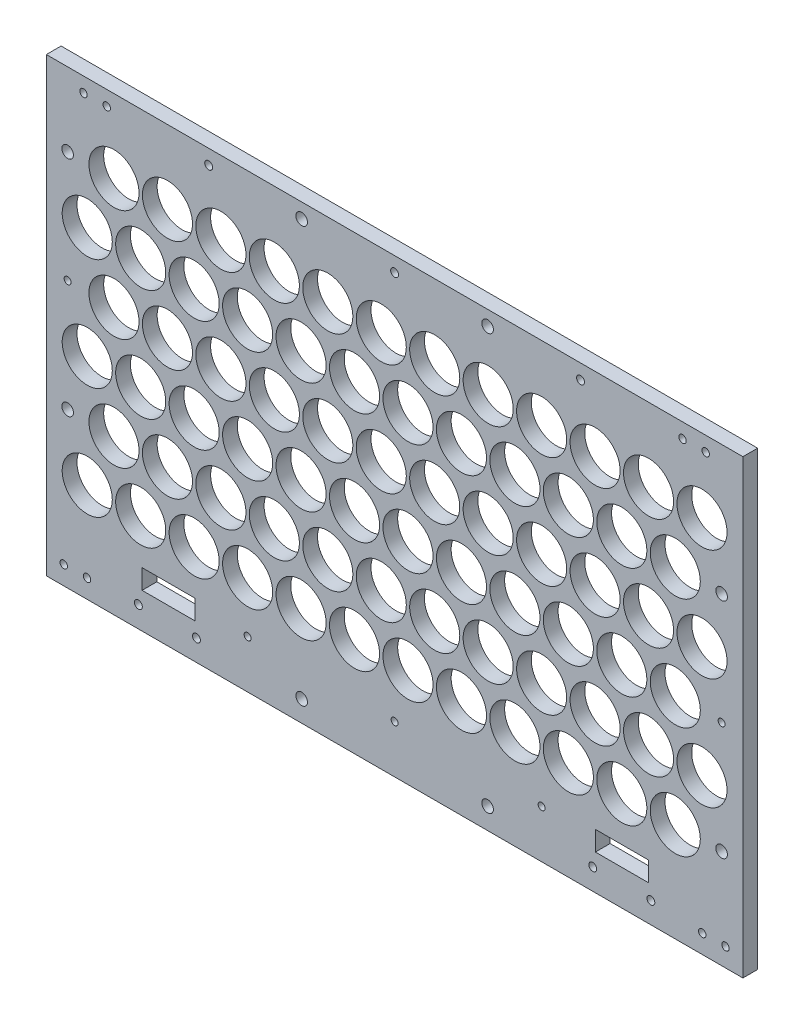
SolidWorks part; units mm, degrees
material "ABS"
ref_plane "X-Y Datum" through (0, 0, 0) normal (0, 0, 1) x (1, 0, 0)
ref_plane "X-Z Datum" through (0, 0, 0) normal (0, 1, 0) x (1, 0, 0)
ref_plane "Y-Z Datum" through (0, 0, 0) normal (1, 0, 0) x (0, 0, -1)
sketch "Sketch1" plane through (0, 0, 0) normal (0, 0, 1) x (1, 0, 0)
  line L1 (-143.025, 70.775) -> (143.025, 70.775)
  line L2 (-143.025, 70.775) -> (-143.025, -70.775)
  line L3 (-143.025, -70.775) -> (143.025, -70.775)
  line L4 (143.025, 70.775) -> (143.025, -70.775)
  line L5 (-143.025, 70.775) -> (143.025, -70.775) construction
  line L6 (-143.025, -70.775) -> (143.025, 70.775) construction
  line L13 (-149.85, -102.6) -> (149.85, -102.6)
  line L14 (-149.85, 91.65) -> (149.85, 91.65)
  line L15 (-149.85, 91.65) -> (-149.85, -102.6)
  line L16 (149.85, 91.65) -> (149.85, -102.6)
  line L17 (149.85, 70.775) -> (149.85, -70.775) construction
  line L18 (-143.025, 91.65) -> (143.025, 91.65) construction
  line L19 (-143.025, -102.6) -> (143.025, -102.6) construction
  line L20 (-149.85, 70.775) -> (-149.85, -70.775) construction
  line L21 (-132.25, -60) -> (-109.25, -60) construction
  circle A0 centre (-132.25, -60) radius 10.775
  circle A1 centre (-109.25, -60) radius 10.775 construction
  circle A2 centre (-120.75, -36) radius 10.775
  point P0 (0, 0)
  point P16 (-120.75, -60)
  dimension "D1" = 21.55
  dimension "D2" = 23
  dimension "D3" = 24
  dimension "D5" = 141.55
  dimension "D6" = 286.05
  dimension "D7" = 31.825
  dimension "D8" = 20.875
  dimension "D9" = 6.825
  dimension "D10" = 6.825
extrude "Boss-Extrude1" add sketch "Sketch1" along normal blind 6.35 contours A0 L3 L4 L1 L2 A2 | A2 | A0 | A0 L2 L3 | L1 L4 L3 L2 region at (2.4105, 0.9241, 0) region at (-140.6182, -68.3682, 0) region at (-132.25, -60, 0) region at (-146.2785, -5.475, 0) region at (-120.75, -36, 0)
sketch "Sketch3" plane through (0, 0, 6.35) normal (0, 0, 1) x (1, 0, 0)
  line L4 (143.025, 70.775) -> (-143.025, 70.775)
  line L5 (143.025, -70.775) -> (143.025, 70.775)
  line L6 (-143.025, -70.775) -> (143.025, -70.775)
  line L7 (-143.025, 70.775) -> (-143.025, -70.775)
  line L8 (143.025, 70.775) -> (-143.025, 70.775)
  line L9 (143.025, -70.775) -> (143.025, 70.775)
  line L10 (-143.025, -70.775) -> (143.025, -70.775)
  line L11 (-143.025, 70.775) -> (-143.025, -70.775)
  circle A1 centre (-120.75, -36) radius 10.775
  circle A2 centre (-120.75, -36) radius 10.775
  circle A3 centre (-132.25, -60) radius 10.775
  circle A4 centre (-132.25, -60) radius 10.775
  dimension "D1" = 0
  dimension "D2" = 0
  dimension "D3" = 0
extrude "Cut-Extrude1" cut sketch "Sketch3" against normal through all contours A4 region at (-132.25, -60, 6.35)
sketch "Sketch4" plane through (0, 0, 6.35) normal (0, 0, 1) x (1, 0, 0)
  line L4 (143.025, 70.775) -> (-143.025, 70.775)
  line L5 (143.025, -70.775) -> (143.025, 70.775)
  line L6 (-143.025, -70.775) -> (143.025, -70.775)
  line L7 (-143.025, 70.775) -> (-143.025, -70.775)
  line L8 (143.025, 70.775) -> (-143.025, 70.775)
  line L9 (143.025, -70.775) -> (143.025, 70.775)
  line L10 (-143.025, -70.775) -> (143.025, -70.775)
  line L11 (-143.025, 70.775) -> (-143.025, -70.775)
  circle A1 centre (-120.75, -36) radius 10.775
  circle A2 centre (-120.75, -36) radius 10.775
  circle A3 centre (-132.25, -60) radius 10.775
  circle A4 centre (-132.25, -60) radius 10.775
  dimension "D1" = 0
  dimension "D2" = 0
  dimension "D3" = 0
extrude "Cut-Extrude2" cut sketch "Sketch4" against normal through all contours A2 region at (-120.75, -36, 6.35)
pattern_linear "LPattern1" count 12 spacing 23 along (1, 0, 0) of "Cut-Extrude1", "Cut-Extrude2"
pattern_linear "LPattern2" count 3 spacing 48 along (0, 1, 0) of "LPattern1"
sketch "Sketch5" plane through (0, 0, 6.35) normal (0, 0, 1) x (1, 0, 0)
  line L4 (105.3154, -79.3475) -> (90.1846, -79.3475)
  line L5 (90.37, -80.3) -> (90.37, -83.4115)
  line L6 (90.37, -83.4115) -> (105.13, -83.4115)
  line L7 (105.13, -83.4115) -> (105.13, -80.3)
  line L8 (105.3154, -79.3475) -> (90.1846, -79.3475)
  line L9 (90.37, -80.3) -> (90.37, -83.4115)
  line L10 (90.37, -83.4115) -> (105.13, -83.4115)
  line L11 (105.13, -83.4115) -> (105.13, -80.3)
  line L12 (-108.668, -78.95) -> (-108.668, -87.4115)
  line L13 (-108.668, -87.4115) -> (-85.908, -87.4115)
  line L14 (-85.908, -87.4115) -> (-85.908, -78.95)
  line L15 (86.37, -78.95) -> (86.37, -87.4115)
  line L16 (-89.7226, -79.3475) -> (-104.8534, -79.3475)
  line L17 (-104.668, -80.3) -> (-104.668, -83.4115)
  line L18 (-104.668, -83.4115) -> (-89.908, -83.4115)
  line L19 (-89.908, -83.4115) -> (-89.908, -80.3)
  line L20 (-89.7226, -79.3475) -> (-104.8534, -79.3475)
  line L21 (-104.668, -80.3) -> (-104.668, -83.4115)
  line L22 (-104.668, -83.4115) -> (-89.908, -83.4115)
  line L23 (-89.908, -83.4115) -> (-89.908, -80.3)
  line L24 (86.37, -87.4115) -> (109.13, -87.4115)
  line L25 (109.13, -87.4115) -> (109.13, -78.95)
  line L26 (149.85, -78.95) -> (-149.85, -78.95) construction
  line L27 (149.85, -78.95) -> (-149.85, -78.95)
  line L28 (109.13, -87.4115) -> (109.13, -80.3) construction
  line L29 (86.37, -80.3) -> (86.37, -87.4115) construction
  line L30 (-85.908, -87.4115) -> (-85.908, -80.3) construction
  line L31 (-108.668, -80.3) -> (-108.668, -87.4115) construction
  arc A2 (90.37, -80.3) -> (90.1846, -79.3475) centre (87.83, -80.3) ccw
  arc A3 (105.3154, -79.3475) -> (105.13, -80.3) centre (107.67, -80.3) ccw
  arc A4 (90.37, -80.3) -> (90.1846, -79.3475) centre (87.83, -80.3) ccw
  arc A5 (105.3154, -79.3475) -> (105.13, -80.3) centre (107.67, -80.3) ccw
  arc A8 (-104.668, -80.3) -> (-104.8534, -79.3475) centre (-107.208, -80.3) ccw
  arc A9 (-89.7226, -79.3475) -> (-89.908, -80.3) centre (-87.368, -80.3) ccw
  arc A10 (-104.668, -80.3) -> (-104.8534, -79.3475) centre (-107.208, -80.3) ccw
  arc A11 (-89.7226, -79.3475) -> (-89.908, -80.3) centre (-87.368, -80.3) ccw
  dimension "D1" = 0
  dimension "D2" = 0
  dimension "D3" = 4
extrude "Cut-Extrude3" cut sketch "Sketch5" against normal through all contours L25 L27 L15 L24 L8 A5 L11 L10 L9 A4 | A5 L8 A4 L9 L10 L11 | L14 L27 L12 L13 L20 A11 L23 L22 L21 A10 | A11 L20 A10 L21 L22 L23 region at (97.75, -81.376, 6.35) region at (-97.288, -83.9995, 6.35) region at (97.75, -83.9995, 6.35) region at (-97.288, -81.376, 6.35)
sketch "Sketch7" plane through (0, 0, 6.35) normal (0, 0, 1) x (1, 0, 0)
  line L0 (0, -3.4925) -> (0, 3.4925) construction
  point P0 (0, 85.3)
  point P1 (-80, 85.3)
  point P3 (-123.85, 85.3)
  point P5 (-133.85, 85.3)
  point P7 (-132.35, -94.6)
  point P9 (-142.35, -94.6)
  point P11 (132.35, -94.6)
  point P13 (142.35, -94.6)
  point P17 (123.85, 85.3)
  point P19 (133.85, 85.3)
  point P21 (110.25, -93.5057)
  point P23 (85.25, -93.5057)
  point P28 (80, 85.3)
  point P29 (-110.25, -93.5057)
  point P31 (-85.25, -93.5057)
hole_wizard "M3 Clearance Hole1" positions "Sketch8" profile "Sketch9" hole size "M3" standard "ANSI Metric" end condition through all
sketch "Sketch8" plane through (0, 0, 6.35) normal (0, 0, 1) x (1, 0, 0)
  point P3 (123.85, 85.3)
  point P6 (133.85, 85.3)
  point P12 (-123.85, 85.3)
  point P15 (-133.85, 85.3)
  point P18 (-142.35, -94.6)
  point P21 (-132.35, -94.6)
  point P24 (132.35, -94.6)
  point P27 (142.35, -94.6)
sketch "Sketch9" plane through (123.85, 85.3, 6.35) normal (1, 0, 0) x (0, -1, 0)
  line L0 (0, 0) -> (0, 6.35)
  line L1 (0, 6.35) -> (1.6, 6.35)
  line L2 (1.6, 6.35) -> (1.6, 0)
  line L5 (1.6, 0) -> (0, 0)
  line L11 (0, -6.35) -> (0, 107.95) construction
  dimension "Thru Hole Dia." = 3.2
  dimension "Thru Hole Depth" = 6.35
hole_wizard "M3 Clearance Hole2" positions "Sketch12" profile "Sketch13" hole size "M3" standard "ANSI Metric" end condition through all
sketch "Sketch12" plane through (0, 0, 6.35) normal (0, 0, 1) x (1, 0, 0)
  point P0 (110.25, -93.5057)
  point P3 (85.25, -93.5057)
  point P6 (80, 85.3)
  point P9 (0, 85.3)
  point P12 (-80, 85.3)
  point P16 (-85.25, -93.5057)
  point P19 (-110.25, -93.5057)
sketch "Sketch13" plane through (110.25, -93.5057, 6.35) normal (1, 0, 0) x (0, -1, 0)
  line L0 (0, 0) -> (0, 6.35)
  line L1 (0, 6.35) -> (1.7, 6.35)
  line L2 (1.7, 6.35) -> (1.7, 0)
  line L5 (1.7, 0) -> (0, 0)
  line L11 (0, -6.35) -> (0, 107.95) construction
  dimension "Thru Hole Dia." = 3.4
  dimension "Thru Hole Depth" = 6.35
sketch "Sketch14" plane through (0, 0, 6.35) normal (0, 0, 1) x (1, 0, 0)
  line L0 (131.525, -12) -> (149.85, -12) construction
  line L1 (149.85, 91.65) -> (149.85, -102.6) construction
  line L2 (-131.525, 12) -> (-149.85, 12) construction
  line L3 (-149.85, 91.65) -> (-149.85, -102.6) construction
  line L4 (149.85, -78.95) -> (-149.85, -78.95) construction
  line L5 (149.85, -78.95) -> (-149.85, -78.95) construction
  line L6 (149.85, -81.95) -> (-149.85, -81.95) construction
  line L7 (68.55, -70.9014) -> (57.95, -70.9014) construction
  line L8 (68.55, -67.0427) -> (68.55, -74.76) construction
  line L9 (57.95, -67.0427) -> (57.95, -74.76) construction
  line L10 (63.25, -70.9014) -> (63.25, -81.95) construction
  line L18 (0, -3.4925) -> (0, 3.4925) construction
  circle A0 centre (120.75, -12) radius 10.775 construction
  circle A1 centre (-120.75, 12) radius 10.775 construction
  circle A2 centre (140.6875, -12) radius 1.5
  circle A3 centre (-140.6875, 12) radius 1.5
  circle A4 centre (63.25, -81.95) radius 1.5
  circle A6 centre (-63.25, -81.95) radius 1.5
  circle A8 centre (0, -81.95) radius 1.5
  dimension "D1" = 3
  dimension "D3" = 3
  dimension "D2" = 3
extrude "Cut-Extrude4" cut sketch "Sketch14" against normal through all
sketch "Sketch15" plane through (0, 0, 6.35) normal (0, 0, 1) x (1, 0, 0)
  line L0 (-6.35, 85.3) -> (-73.65, 85.3) construction
  line L1 (-6.35, 90.65) -> (-6.35, 79.95) construction
  line L2 (-73.65, 79.95) -> (-73.65, 90.65) construction
  line L3 (73.65, 85.3) -> (6.35, 85.3) construction
  line L4 (73.65, 90.65) -> (73.65, 79.95) construction
  line L5 (6.35, 79.95) -> (6.35, 90.65) construction
  line L6 (131.525, 36) -> (149.85, 36) construction
  line L7 (149.85, 91.65) -> (149.85, -105.775) construction
  line L8 (131.525, -60) -> (149.85, -60) construction
  line L9 (-131.525, -36) -> (-149.85, -36) construction
  line L10 (-149.85, -105.775) -> (-149.85, 91.65) construction
  line L11 (-131.525, 60) -> (-149.85, 60) construction
  line L12 (40, 85.3) -> (40, -102.6) construction
  line L13 (-149.85, -102.6) -> (149.85, -102.6) construction
  line L14 (-40, 85.3) -> (-40, -102.6) construction
  line L16 (85.25, -93.5057) -> (-85.25, -93.5057) construction
  circle A0 centre (40, 85.3) radius 2.5
  circle A1 centre (-40, 85.3) radius 2.5
  circle A2 centre (120.75, 36) radius 10.775 construction
  circle A3 centre (120.75, -60) radius 10.775 construction
  circle A4 centre (140.6875, 36) radius 2.5
  circle A5 centre (140.6875, -60) radius 2.5
  circle A6 centre (-120.75, -36) radius 10.775 construction
  circle A7 centre (-120.75, 60) radius 10.775 construction
  circle A8 centre (-140.6875, -36) radius 2.5
  circle A9 centre (-140.6875, 60) radius 2.5
  circle A10 centre (40, -93.5057) radius 2.5
  circle A11 centre (-40, -93.5057) radius 2.5
  dimension "D1" = 5
extrude "Cut-Extrude5" cut sketch "Sketch15" against normal through all
